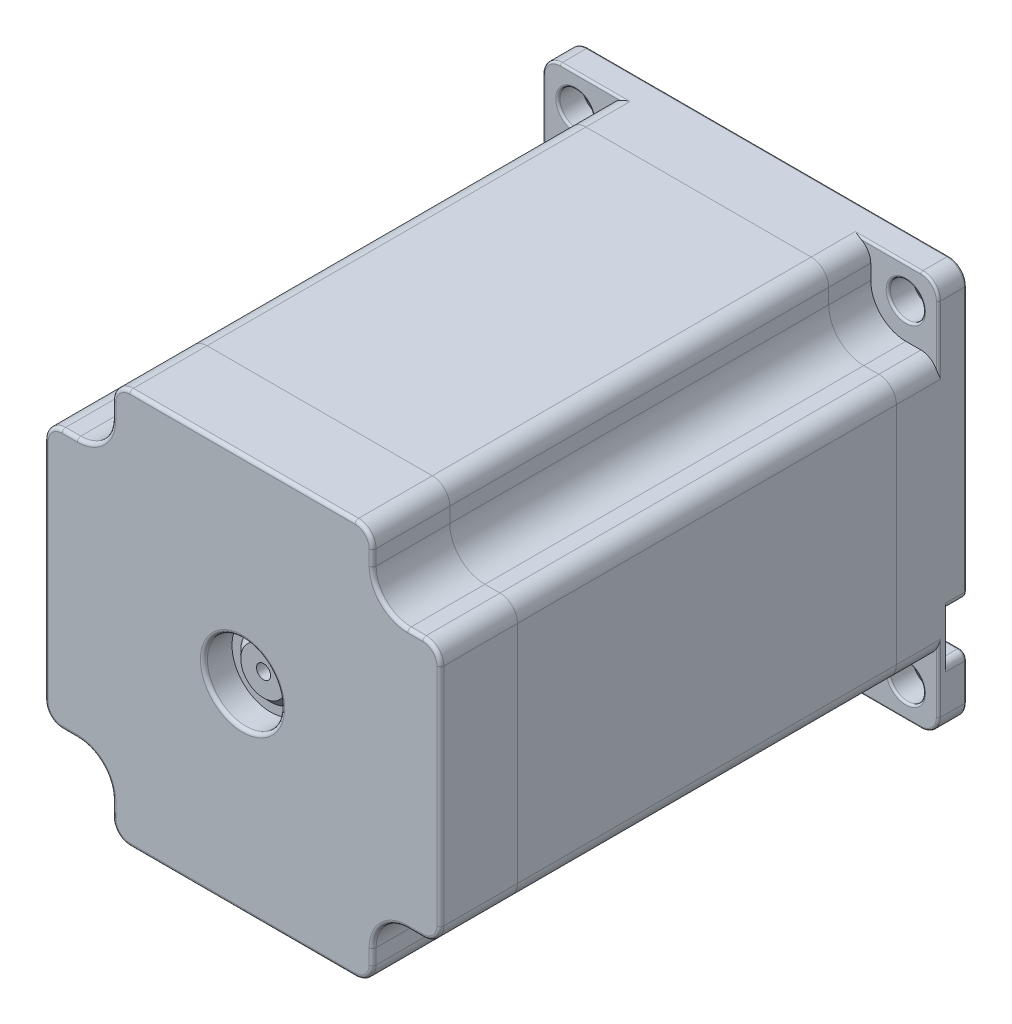
SolidWorks part; units mm, degrees
material "Alloy Steel"
ref_plane "Спереди" through (0, 0, 0) normal (0, 0, 1) x (1, 0, 0)
ref_plane "Сверху" through (0, 0, 0) normal (0, 1, 0) x (1, 0, 0)
ref_plane "Справа" through (0, 0, 0) normal (1, 0, 0) x (0, 0, -1)
sketch "Эскиз1" plane through (0, 0, 0) normal (0, 0, 1) x (1, 0, 0)
  line L1 (-28.2, -28.2) -> (28.2, -28.2)
  line L2 (-28.2, -28.2) -> (-28.2, 28.2)
  line L3 (-28.2, 28.2) -> (28.2, 28.2)
  line L4 (28.2, -28.2) -> (28.2, 28.2)
  line L5 (-28.2, -28.2) -> (28.2, 28.2) construction
  line L6 (-28.2, 28.2) -> (28.2, -28.2) construction
  point P0 (0, 0)
  dimension "D1" = 56.4
extrude "Бобышка-Вытянуть1" add sketch "Эскиз1" along normal blind 10
sketch "Эскиз2" plane through (0, 0, 10) normal (0, 0, 1) x (1, 0, 0)
  line L1 (-23.55, -23.55) -> (23.55, -23.55) construction
  line L2 (-23.55, -23.55) -> (-23.55, 23.55) construction
  line L3 (-23.55, 23.55) -> (23.55, 23.55) construction
  line L4 (23.55, -23.55) -> (23.55, 23.55) construction
  line L5 (-23.55, -23.55) -> (23.55, 23.55) construction
  line L6 (-23.55, 23.55) -> (23.55, -23.55) construction
  circle A0 centre (-23.55, 23.55) radius 2.5
  circle A1 centre (23.55, 23.55) radius 2.5
  circle A2 centre (23.55, -23.55) radius 2.5
  circle A3 centre (-23.55, -23.55) radius 2.5
  point P0 (0, 0)
  dimension "D1" = 5
  dimension "D2" = 47.1
extrude "Вырез-Вытянуть1" cut sketch "Эскиз2" against normal through all
sketch "Эскиз3" plane through (0, 0, 10) normal (0, 0, 1) x (1, 0, 0)
  line L0 (-18.55, 23.55) -> (-18.55, 28.2)
  line L1 (28.2, 28.2) -> (-28.2, 28.2) construction
  line L2 (-18.55, 28.2) -> (-28.2, 28.2)
  line L3 (-28.2, 28.2) -> (-28.2, 18.55)
  line L4 (-28.2, 28.2) -> (-28.2, -28.2) construction
  line L5 (-28.2, 18.55) -> (-23.55, 18.55)
  line L6 (18.55, 23.55) -> (18.55, 28.2)
  line L7 (18.55, 28.2) -> (28.2, 28.2)
  line L8 (28.2, 28.2) -> (28.2, 18.55)
  line L9 (28.2, -28.2) -> (28.2, 28.2) construction
  line L10 (28.2, 18.55) -> (23.55, 18.55)
  line L11 (18.55, -23.55) -> (18.55, -28.2)
  line L12 (-28.2, -28.2) -> (28.2, -28.2) construction
  line L13 (18.55, -28.2) -> (28.2, -28.2)
  line L14 (28.2, -28.2) -> (28.2, -18.55)
  line L15 (28.2, -18.55) -> (23.55, -18.55)
  line L16 (-23.55, -18.55) -> (-28.2, -18.55)
  line L17 (-28.2, -18.55) -> (-28.2, -28.2)
  line L18 (-28.2, -28.2) -> (-18.55, -28.2)
  line L19 (-18.55, -28.2) -> (-18.55, -23.55)
  arc A0 (-23.55, 18.55) -> (-18.55, 23.55) centre (-23.55, 23.55) ccw
  arc A1 (18.55, 23.55) -> (23.55, 18.55) centre (23.55, 23.55) ccw
  arc A2 (23.55, -18.55) -> (18.55, -23.55) centre (23.55, -23.55) ccw
  arc A3 (-18.55, -23.55) -> (-23.55, -18.55) centre (-23.55, -23.55) ccw
  dimension "D1" = 10
extrude "Вырез-Вытянуть2" cut sketch "Эскиз3" against normal blind 6
fillet "Скругление1" radius 2.5 12 edges at (28.2, -28.2, 2) (28.2, -18.55, 7) (18.55, -28.2, 7) (-18.55, -28.2, 7) (-28.2, -18.55, 7) (-28.2, -28.2, 2) (-28.2, 18.55, 7) (-18.55, 28.2, 7) (-28.2, 28.2, 2) (28.2, 18.55, 7) (18.55, 28.2, 7) (28.2, 28.2, 2)
sketch "Эскиз4" plane through (0, 0, 0) normal (0, 0, -1) x (-1, 0, 0)
  circle A0 centre (0, 0) radius 19.05
  dimension "D1" = 38.1
extrude "Бобышка-Вытянуть2" add sketch "Эскиз4" along normal blind 1.6
sketch "Эскиз5" plane through (0, 0, 0) normal (0, 0, -1) x (-1, 0, 0)
  circle A0 centre (0, 0) radius 3.175
  dimension "D1" = 6.35
extrude "Бобышка-Вытянуть3" add sketch "Эскиз5" along normal blind 20.6
sketch "Эскиз6" plane through (0, 0, -1.6) normal (0, 0, -1) x (-1, 0, 0)
  circle A0 centre (0, 0) radius 5.5
  circle A1 centre (0, 0) radius 3.175 construction
  circle A2 centre (0, 0) radius 3.175
  dimension "D1" = 11
extrude "Вырез-Вытянуть3" cut sketch "Эскиз6" against normal blind 2.5
chamfer "Фаска1" distance 0.5 angle 45 5 edges at (-3.175, 0, -20.6) (26.05, -23.55, 0) (-21.05, -23.55, 0) (-21.05, 23.55, 0) (26.05, 23.55, 0)
sketch "Эскиз7" plane through (0, 0, -20.6) normal (0, 0, -1) x (-1, 0, 0)
  circle A0 centre (0, 0) radius 1
  dimension "D1" = 2
extrude "Вырез-Вытянуть4" cut sketch "Эскиз7" against normal blind 3
sketch "Эскиз8" plane through (0, 0, 0) normal (0, 0, -1) x (-1, 0, 0)
  line L0 (-28.2, -16.2) -> (-25.45, -16.2) construction
  line L1 (-28.2, -25.7) -> (-28.2, 25.7) construction
  line L2 (-28.2, -12.95) -> (-25.45, -12.95)
  line L3 (-28.2, -19.45) -> (-25.45, -19.45)
  line L4 (25.7, -28.2) -> (-25.7, -28.2) construction
  arc A0 (-28.2, -12.95) -> (-28.2, -19.45) centre (-28.2, -16.2) ccw
  arc A1 (-25.45, -19.45) -> (-25.45, -12.95) centre (-25.45, -16.2) ccw
  point P4 (-26.825, -16.2)
  dimension "D1" = 3.25
  dimension "D2" = 6
  dimension "D3" = 12
extrude "Вырез-Вытянуть5" cut sketch "Эскиз8" against normal blind 3
fillet "Скругление2" radius 1 2 edges at (28.2, -19.45, 1.5) (28.2, -12.95, 1.5)
sketch "Эскиз9" plane through (0, 0, 3) normal (0, 0, -1) x (-1, 0, 0)
  circle A0 centre (-25.45, -16.2) radius 2.5
  dimension "D1" = 5
extrude "Бобышка-Вытянуть4" [suppressed] add sketch "Эскиз9" along normal blind 2 separate body
fillet "Скругление3" [suppressed] radius 1.5
fillet "Скругление4" [suppressed] radius 0.5
sketch "Эскиз10" [suppressed] plane through (0, 0, 1) normal (0, 0, -1) x (-1, 0, 0)
  line L0 (-25.05, -15.3) -> (-25.05, -14.2)
  line L1 (-25.85, -18.2) -> (-25.05, -18.2)
  line L2 (-25.85, -18.2) -> (-25.85, -17.1)
  line L3 (-25.85, -14.2) -> (-25.05, -14.2)
  line L4 (-25.05, -18.2) -> (-25.05, -17.1)
  line L5 (-25.85, -18.2) -> (-25.05, -14.2) construction
  line L6 (-25.85, -14.2) -> (-25.05, -18.2) construction
  line L7 (-27.45, -16.6) -> (-26.35, -16.6)
  line L8 (-27.45, -16.6) -> (-27.45, -15.8)
  line L9 (-27.45, -15.8) -> (-26.35, -15.8)
  line L10 (-23.45, -16.6) -> (-23.45, -15.8)
  line L11 (-27.45, -16.6) -> (-23.45, -15.8) construction
  line L12 (-27.45, -15.8) -> (-23.45, -16.6) construction
  line L13 (-24.55, -15.8) -> (-23.45, -15.8)
  line L14 (-25.85, -15.3) -> (-25.85, -14.2)
  line L15 (-24.55, -16.6) -> (-23.45, -16.6)
  arc A0 (-25.85, -17.1) -> (-26.35, -16.6) centre (-26.35, -17.1) ccw
  arc A1 (-25.05, -17.1) -> (-24.55, -16.6) centre (-24.55, -17.1) cw
  arc A2 (-25.05, -15.3) -> (-24.55, -15.8) centre (-24.55, -15.3) ccw
  arc A3 (-26.35, -15.8) -> (-25.85, -15.3) centre (-26.35, -15.3) ccw
  point P0 (-25.45, -16.2)
  point P6 (-25.45, -16.2)
  point P19 (-25.05, -16.6)
  point P22 (-25.05, -15.8)
  point P25 (-25.85, -15.8)
  dimension "D4" = 0.5
  dimension "D1" = 4
  dimension "D2" = 4
  dimension "D3" = 0.8
extrude "Вырез-Вытянуть6" [suppressed] cut sketch "Эскиз10" against normal blind 1.5 draft 13
fillet "Скругление5" [suppressed] radius 0.5
fillet "Скругление6" [suppressed] radius 0.2
ref_axis "Ось1" through (0, 0, 50) along (0, 0, -1)
pattern_circular "Круговой массив2" [suppressed] count 4 over 360 about axis through (0, 0, 50) along (0, 0, -1) of bodies 110
sketch "Эскиз11" plane through (0, 0, 10) normal (0, 0, 1) x (1, 0, 0)
  line L12 (23.55, -18.55) -> (25.7, -18.55)
  line L13 (28.2, -16.05) -> (28.2, 16.05)
  line L14 (25.7, 18.55) -> (23.55, 18.55)
  line L15 (18.55, 23.55) -> (18.55, 25.7)
  line L16 (16.05, 28.2) -> (-16.05, 28.2)
  line L17 (-18.55, 25.7) -> (-18.55, 23.55)
  line L18 (-23.55, 18.55) -> (-25.7, 18.55)
  line L19 (-28.2, 16.05) -> (-28.2, -16.05)
  line L20 (-25.7, -18.55) -> (-23.55, -18.55)
  line L21 (-18.55, -23.55) -> (-18.55, -25.7)
  line L22 (-16.05, -28.2) -> (16.05, -28.2)
  line L23 (18.55, -25.7) -> (18.55, -23.55)
  line L24 (23.55, -18.55) -> (25.7, -18.55)
  line L25 (28.2, -16.05) -> (28.2, 16.05)
  line L26 (25.7, 18.55) -> (23.55, 18.55)
  line L27 (18.55, 23.55) -> (18.55, 25.7)
  line L28 (16.05, 28.2) -> (-16.05, 28.2)
  line L29 (-18.55, 25.7) -> (-18.55, 23.55)
  line L30 (-23.55, 18.55) -> (-25.7, 18.55)
  line L31 (-28.2, 16.05) -> (-28.2, -16.05)
  line L32 (-25.7, -18.55) -> (-23.55, -18.55)
  line L33 (-18.55, -23.55) -> (-18.55, -25.7)
  line L34 (-16.05, -28.2) -> (16.05, -28.2)
  line L35 (18.55, -25.7) -> (18.55, -23.55)
  arc A12 (25.7, -18.55) -> (28.2, -16.05) centre (25.7, -16.05) ccw
  arc A13 (28.2, 16.05) -> (25.7, 18.55) centre (25.7, 16.05) ccw
  arc A14 (18.55, 23.55) -> (23.55, 18.55) centre (23.55, 23.55) ccw
  arc A15 (18.55, 25.7) -> (16.05, 28.2) centre (16.05, 25.7) ccw
  arc A16 (-16.05, 28.2) -> (-18.55, 25.7) centre (-16.05, 25.7) ccw
  arc A17 (-23.55, 18.55) -> (-18.55, 23.55) centre (-23.55, 23.55) ccw
  arc A18 (-25.7, 18.55) -> (-28.2, 16.05) centre (-25.7, 16.05) ccw
  arc A19 (-28.2, -16.05) -> (-25.7, -18.55) centre (-25.7, -16.05) ccw
  arc A20 (-18.55, -23.55) -> (-23.55, -18.55) centre (-23.55, -23.55) ccw
  arc A21 (-18.55, -25.7) -> (-16.05, -28.2) centre (-16.05, -25.7) ccw
  arc A22 (16.05, -28.2) -> (18.55, -25.7) centre (16.05, -25.7) ccw
  arc A23 (23.55, -18.55) -> (18.55, -23.55) centre (23.55, -23.55) ccw
  arc A24 (25.7, -18.55) -> (28.2, -16.05) centre (25.7, -16.05) ccw
  arc A25 (28.2, 16.05) -> (25.7, 18.55) centre (25.7, 16.05) ccw
  arc A26 (18.55, 23.55) -> (23.55, 18.55) centre (23.55, 23.55) ccw
  arc A27 (18.55, 25.7) -> (16.05, 28.2) centre (16.05, 25.7) ccw
  arc A28 (-16.05, 28.2) -> (-18.55, 25.7) centre (-16.05, 25.7) ccw
  arc A29 (-23.55, 18.55) -> (-18.55, 23.55) centre (-23.55, 23.55) ccw
  arc A30 (-25.7, 18.55) -> (-28.2, 16.05) centre (-25.7, 16.05) ccw
  arc A31 (-28.2, -16.05) -> (-25.7, -18.55) centre (-25.7, -16.05) ccw
  arc A32 (-18.55, -23.55) -> (-23.55, -18.55) centre (-23.55, -23.55) ccw
  arc A33 (-18.55, -25.7) -> (-16.05, -28.2) centre (-16.05, -25.7) ccw
  arc A34 (16.05, -28.2) -> (18.55, -25.7) centre (16.05, -25.7) ccw
  arc A35 (23.55, -18.55) -> (18.55, -23.55) centre (23.55, -23.55) ccw
  dimension "D1" = 0
extrude "Бобышка-Вытянуть5" add sketch "Эскиз11" along normal blind 54 separate body
sketch "Эскиз12" plane through (0, 0, 64) normal (0, 0, 1) x (1, 0, 0)
  line L12 (23.55, -18.55) -> (25.7, -18.55)
  line L13 (28.2, -16.05) -> (28.2, 16.05)
  line L14 (25.7, 18.55) -> (23.55, 18.55)
  line L15 (18.55, 23.55) -> (18.55, 25.7)
  line L16 (16.05, 28.2) -> (-16.05, 28.2)
  line L17 (-18.55, 25.7) -> (-18.55, 23.55)
  line L18 (-23.55, 18.55) -> (-25.7, 18.55)
  line L19 (-28.2, 16.05) -> (-28.2, -16.05)
  line L20 (-25.7, -18.55) -> (-23.55, -18.55)
  line L21 (-18.55, -23.55) -> (-18.55, -25.7)
  line L22 (-16.05, -28.2) -> (16.05, -28.2)
  line L23 (18.55, -25.7) -> (18.55, -23.55)
  line L24 (23.55, -18.55) -> (25.7, -18.55)
  line L25 (28.2, -16.05) -> (28.2, 16.05)
  line L26 (25.7, 18.55) -> (23.55, 18.55)
  line L27 (18.55, 23.55) -> (18.55, 25.7)
  line L28 (16.05, 28.2) -> (-16.05, 28.2)
  line L29 (-18.55, 25.7) -> (-18.55, 23.55)
  line L30 (-23.55, 18.55) -> (-25.7, 18.55)
  line L31 (-28.2, 16.05) -> (-28.2, -16.05)
  line L32 (-25.7, -18.55) -> (-23.55, -18.55)
  line L33 (-18.55, -23.55) -> (-18.55, -25.7)
  line L34 (-16.05, -28.2) -> (16.05, -28.2)
  line L35 (18.55, -25.7) -> (18.55, -23.55)
  arc A12 (23.55, -18.55) -> (18.55, -23.55) centre (23.55, -23.55) ccw
  arc A13 (25.7, -18.55) -> (28.2, -16.05) centre (25.7, -16.05) ccw
  arc A14 (28.2, 16.05) -> (25.7, 18.55) centre (25.7, 16.05) ccw
  arc A15 (18.55, 23.55) -> (23.55, 18.55) centre (23.55, 23.55) ccw
  arc A16 (18.55, 25.7) -> (16.05, 28.2) centre (16.05, 25.7) ccw
  arc A17 (-16.05, 28.2) -> (-18.55, 25.7) centre (-16.05, 25.7) ccw
  arc A18 (-23.55, 18.55) -> (-18.55, 23.55) centre (-23.55, 23.55) ccw
  arc A19 (-25.7, 18.55) -> (-28.2, 16.05) centre (-25.7, 16.05) ccw
  arc A20 (-28.2, -16.05) -> (-25.7, -18.55) centre (-25.7, -16.05) ccw
  arc A21 (-18.55, -23.55) -> (-23.55, -18.55) centre (-23.55, -23.55) ccw
  arc A22 (-18.55, -25.7) -> (-16.05, -28.2) centre (-16.05, -25.7) ccw
  arc A23 (16.05, -28.2) -> (18.55, -25.7) centre (16.05, -25.7) ccw
  arc A24 (23.55, -18.55) -> (18.55, -23.55) centre (23.55, -23.55) ccw
  arc A25 (25.7, -18.55) -> (28.2, -16.05) centre (25.7, -16.05) ccw
  arc A26 (28.2, 16.05) -> (25.7, 18.55) centre (25.7, 16.05) ccw
  arc A27 (18.55, 23.55) -> (23.55, 18.55) centre (23.55, 23.55) ccw
  arc A28 (18.55, 25.7) -> (16.05, 28.2) centre (16.05, 25.7) ccw
  arc A29 (-16.05, 28.2) -> (-18.55, 25.7) centre (-16.05, 25.7) ccw
  arc A30 (-23.55, 18.55) -> (-18.55, 23.55) centre (-23.55, 23.55) ccw
  arc A31 (-25.7, 18.55) -> (-28.2, 16.05) centre (-25.7, 16.05) ccw
  arc A32 (-28.2, -16.05) -> (-25.7, -18.55) centre (-25.7, -16.05) ccw
  arc A33 (-18.55, -23.55) -> (-23.55, -18.55) centre (-23.55, -23.55) ccw
  arc A34 (-18.55, -25.7) -> (-16.05, -28.2) centre (-16.05, -25.7) ccw
  arc A35 (16.05, -28.2) -> (18.55, -25.7) centre (16.05, -25.7) ccw
  dimension "D1" = 0
extrude "Бобышка-Вытянуть6" add sketch "Эскиз12" along normal blind 11 separate body
fillet "Скругление7" radius 0.5 24 edges at (27.4678, -17.8178, 75) (24.625, -18.55, 75) (20.0145, -20.0145, 75) (18.55, -24.625, 75) (17.8178, -27.4678, 75) (0, -28.2, 75) (-17.8178, -27.4678, 75) (-18.55, -24.625, 75) (-20.0145, -20.0145, 75) (-24.625, -18.55, 75) (-27.4678, -17.8178, 75) (-28.2, 0, 75) (-27.4678, 17.8178, 75) (-24.625, 18.55, 75) (-20.0145, 20.0145, 75) (-18.55, 24.625, 75) (-17.8178, 27.4678, 75) (0, 28.2, 75) (17.8178, 27.4678, 75) (18.55, 24.625, 75) (20.0145, 20.0145, 75) (24.625, 18.55, 75) (27.4678, 17.8178, 75) (28.2, 0, 75)
sketch "Эскиз13" [suppressed] plane through (0, 0, 75) normal (0, 0, 1) x (1, 0, 0)
  circle A0 centre (16.2, 25.45) radius 1.25
  circle A1 centre (-25.4912, 16.2) radius 1.25
  circle A2 centre (-16.2, -25.45) radius 1.25
  circle A3 centre (25.45, -16.2) radius 1.25
  dimension "D1" = 2.5
extrude "Вырез-Вытянуть7" [suppressed] cut sketch "Эскиз13" against normal blind 2
chamfer "Фаска2" [suppressed] distance 0.2 angle 45
sketch "Эскиз14" plane through (0, 0, 75) normal (0, 0, 1) x (1, 0, 0)
  circle A0 centre (0, 0) radius 5.5
  dimension "D1" = 11
extrude "Вырез-Вытянуть8" cut sketch "Эскиз14" against normal blind 4
sketch "Эскиз15" plane through (0, 0, 71) normal (0, 0, 1) x (1, 0, 0)
  circle A0 centre (0, 0) radius 3.25
  dimension "D1" = 6.5
extrude "Бобышка-Вытянуть7" add sketch "Эскиз15" along normal blind 1
sketch "Эскиз16" plane through (0, 0, 72) normal (0, 0, 1) x (1, 0, 0)
  circle A0 centre (0, 0) radius 1
  dimension "D1" = 2
extrude "Вырез-Вытянуть9" cut sketch "Эскиз16" against normal blind 3
chamfer "Фаска3" distance 1 angle 45 1 edges at (3.25, 0, 71)
fillet "Скругление8" radius 0.5 1 edges at (5.5, 0, 75)
fillet "Скругление9" radius 0.3 33 edges at (-20.875, 28.2, 4) (-27.4678, 27.4678, 4) (-28.2, -20.875, 4) (-27.4678, -27.4678, 4) (20.875, -28.2, 4) (27.4678, -27.4678, 4) (28.2, 20.875, 4) (27.4678, 27.4678, 4) (0, 28.2, 0) (27.4678, 27.4678, 0) (28.2, 6.875, 0) (27.9071, -12.6571, 0) (26.325, -12.95, 0) (22.2, -16.2, 0) (26.325, -19.45, 0) (27.9071, -19.7429, 0) (28.2, -23.075, 0) (27.4678, -27.4678, 0) (0, -28.2, 0) (-27.4678, -27.4678, 0) (-28.2, 0, 0) (-27.4678, 27.4678, 0) (26.05, 23.55, 4) (-21.05, -23.55, 4) (-21.05, 23.55, 4) (-28.2, 20.875, 4) (-20.875, -28.2, 4) (28.2, -20.875, 4) (20.875, 28.2, 4) (26.05, -23.55, 4) (-19.05, 0, 0) (-19.05, 0, -1.6) (-5.5, 0, -1.6)
sketch "Эскиз17" plane through (28.2, 0, 0) normal (1, 0, 0) x (0, 0, -1)
  line L0 (-68.4, -6) -> (-64.4, -6)
  line L1 (-64.4, -6) -> (-64.4, 6)
  line L2 (-64.4, 6) -> (-68.4, 6)
  line L3 (-64, -16.05) -> (-64, 16.05) construction
  arc A0 (-68.4, -6) -> (-68.4, 6) centre (-68.4, 0) cw
  circle A1 centre (-68.4, 0) radius 2.5
  dimension "D2" = 4
  dimension "D4" = 5
  dimension "D1" = 12
  dimension "D3" = 0.4
extrude "Бобышка-Вытянуть8" [suppressed] add sketch "Эскиз17" along normal blind 2 and the other way blind 0.5 separate body
combine bodies "Combine1" [suppressed] operation type add bodies to combine 112 119 110 120 114
